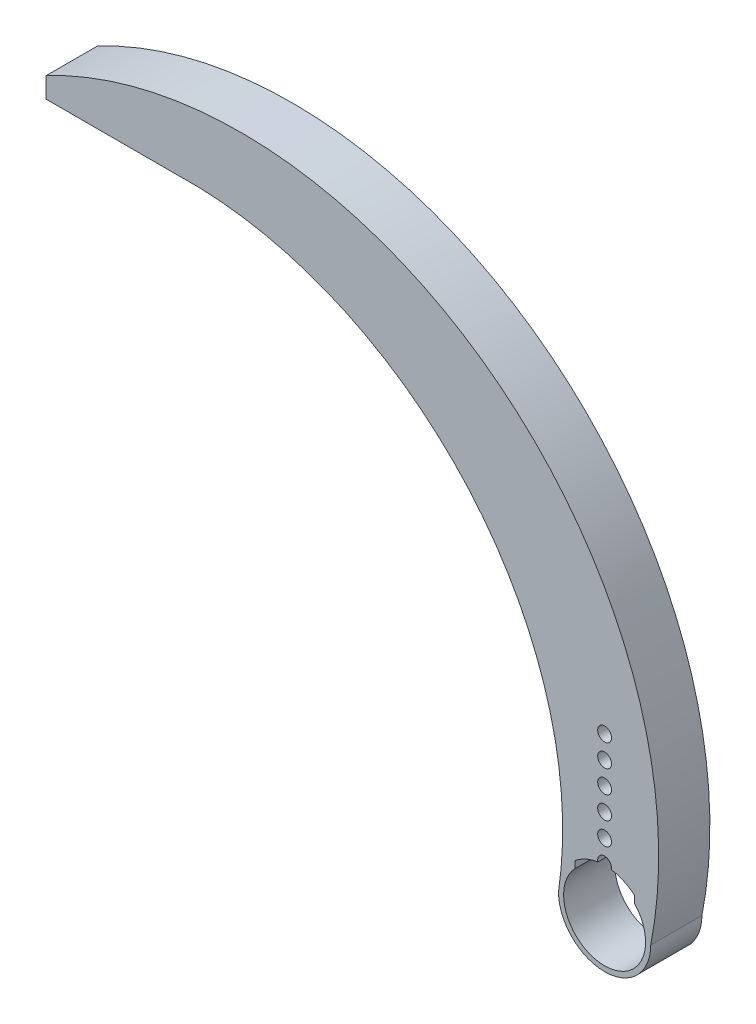
SolidWorks part; units mm, degrees
ref_plane "Front Plane" through (0, 0, 0) normal (0, 0, 1) x (1, 0, 0)
ref_plane "Top Plane" through (0, 0, 0) normal (0, 1, 0) x (1, 0, 0)
ref_plane "Right Plane" through (0, 0, 0) normal (1, 0, 0) x (0, 0, -1)
sketch "Sketch1" plane through (0, 0, 0) normal (0, 0, 1) x (1, 0, 0)
  line L0 (-54.5, 44) -> (-39.5, 44)
  line L1 (2.5, 3.6) -> (2, 15.6)
  line L2 (-2, 15.6) -> (-2.5, 3.6)
  line L3 (-2.5, 3.6) -> (-2.5, 2.5904)
  line L4 (2.5, 2.5904) -> (2.5, 3.6)
  line L5 (0, 15.6) -> (0, 0) construction
  line L6 (-2, 15.6) -> (2, 15.6) construction
  line L7 (2.9, 2.755) -> (2.9, 3.6083)
  line L8 (-39.5, 44) -> (-54.5, 44)
  line L9 (-39.5, 44) -> (-39.5, 42)
  line L10 (-39.5, 42) -> (-54.5, 42)
  line L11 (-54.5, 44) -> (-54.5, 42)
  line L12 (2.9, 3.6083) -> (2.4, 15.6087)
  line L13 (-2.4, 15.6087) -> (-2.9, 3.6083)
  line L14 (-2.9, 3.6083) -> (-2.9, 2.755)
  circle A0 centre (0, 0) radius 1.7
  circle A2 centre (0, 0) radius 4.5
  arc A3 (-39.5, 42) -> (-4.5, 0) centre (-40.6705, 5.4412) cw
  arc A4 (-54.5, 44) -> (4.5, 0) centre (-35.4928, 7.9301) cw
  arc A5 (2, 15.6) -> (-2, 15.6) centre (0, 15.6) ccw
  arc A6 (-2.5, 2.5904) -> (2.5, 2.5904) centre (0, 0) ccw
  circle A8 centre (0, 0) radius 2.5
  circle A9 centre (0, 15.6) radius 0.675
  circle A10 centre (0, 13.4) radius 0.675
  circle A11 centre (0, 11.2) radius 0.675
  circle A12 centre (0, 9) radius 0.675
  circle A13 centre (0, 6.8) radius 0.675
  circle A14 centre (0, 4.6) radius 0.675
  arc A15 (2.4, 15.6087) -> (-2.4, 15.6087) centre (0, 15.6) ccw
  arc A16 (-2.9, 2.755) -> (2.9, 2.755) centre (0, 0) ccw
  point P8 (-47, 44)
  dimension "D1" = 3.4
  dimension "D6" = 5
  dimension "D7" = 3.6
  dimension "D8" = 1.0096
  dimension "D12" = 2
  dimension "D18" = 2.2
  dimension "D19" = 2.2
  dimension "D20" = 2
  dimension "D2" = 9
  dimension "D3" = 15
  dimension "D4" = 47
  dimension "D5" = 44
  dimension "D9" = 1.0096
  dimension "D10" = 12
  dimension "D11" = 12
  dimension "D13" = 15.6
  dimension "D14" = 4.772
  dimension "D15" = 2.2
  dimension "D16" = 2.2
  dimension "D17" = 2.2
  dimension "D21" = 0.4
extrude "Boss-Extrude1" add sketch "Sketch1" along normal blind 5 contours L0 L11 L10 L9 | A15 L12 L7 A2 A4 L0 L9 A3 L14 L13 | A16 L14 A2 A3 L7 region at (-15.8649, 32.9561, 0) region at (-47, 43, 0) region at (0, -4.38, 0)
extrude "Boss-Extrude2" add sketch "Sketch1<3>" against normal blind 2.5 from surface contours A14 A2 L4 L1 A5 L2 L3 A13 A12 A11 A10 A9 | L12 A15 L13 L14 A2 L3 L2 A5 L1 L4 L7 region at (2.7953, 3.7244, 0) region at (0, 10.4623, 0) starting at face at (0, 6.5967, 5)
sketch "Sketch1<3>" plane through (0, 0, 0) normal (0, 0, 1) x (1, 0, 0) same geometry as "Sketch1"
